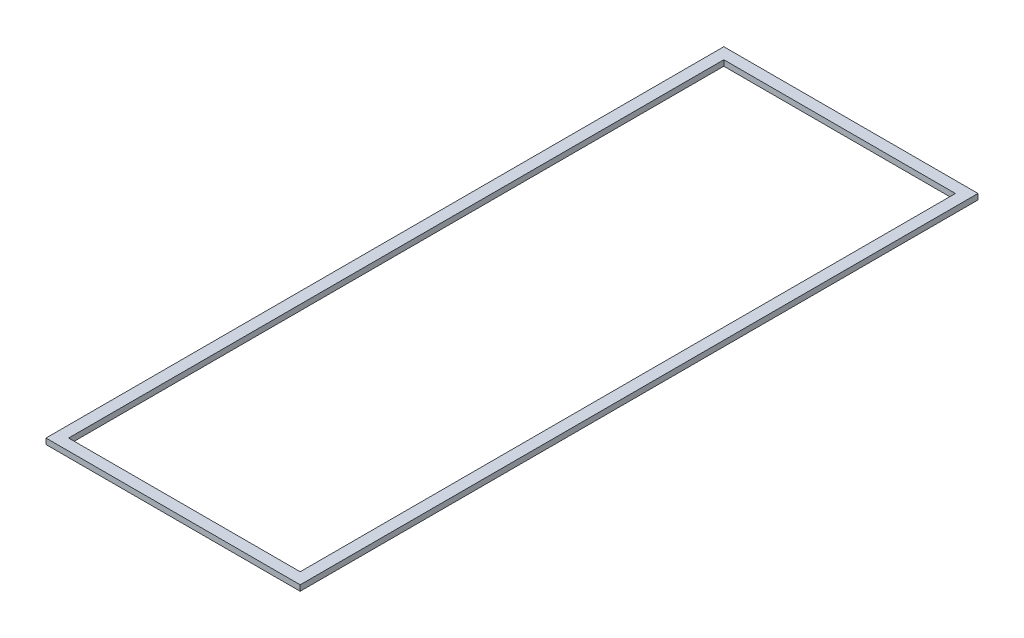
SolidWorks part; units mm, degrees
ref_plane "Спереди" through (0, 0, 0) normal (0, 0, 1) x (1, 0, 0)
ref_plane "Сверху" through (0, 0, 0) normal (0, 1, 0) x (1, 0, 0)
ref_plane "Справа" through (0, 0, 0) normal (1, 0, 0) x (0, 0, -1)
sketch "Эскиз1" plane through (0, 0, 0) normal (0, 1, 0) x (1, 0, 0)
  line L1 (0, 0) -> (450, 0)
  line L2 (0, 0) -> (0, 1200)
  line L3 (0, 1200) -> (450, 1200)
  line L4 (450, 0) -> (450, 1200)
extrude "Вытянуть-Тонкостенный1" add sketch "Эскиз1" along normal blind 10 thin thin type one direction reverse wall 20
